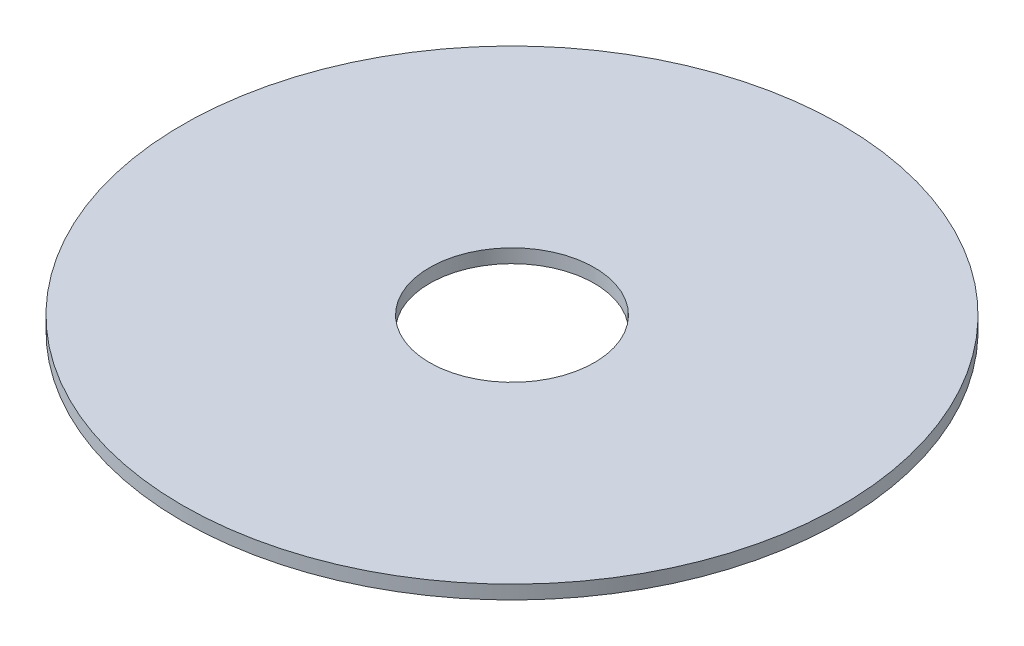
SolidWorks part; units mm, degrees
material "6061 Alloy"
ref_plane "Front Plane" through (0, 0, 0) normal (0, 0, 1) x (1, 0, 0)
ref_plane "Top Plane" through (0, 0, 0) normal (0, 1, 0) x (1, 0, 0)
ref_plane "Right Plane" through (0, 0, 0) normal (1, 0, 0) x (0, 0, -1)
sketch "Sketch1" plane through (0, 0, 0) normal (0, 1, 0) x (1, 0, 0)
  circle A0 centre (0, 0) radius 24
  circle A1 centre (0, 0) radius 6
  dimension "D1" = 12
  dimension "D2" = 48
extrude "Boss-Extrude1" add sketch "Sketch1" along normal blind 1
